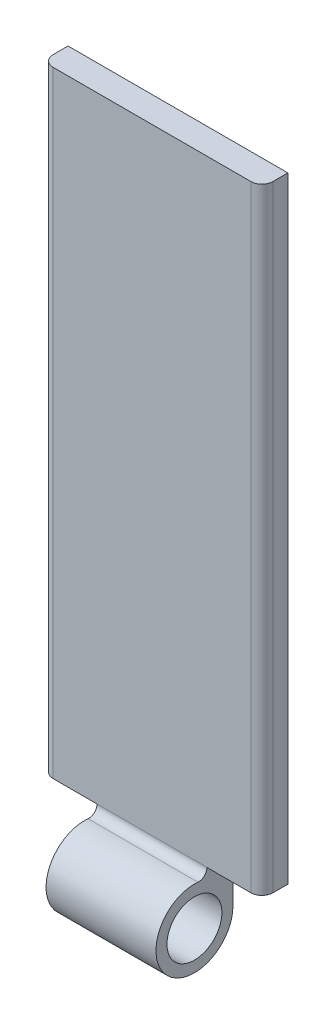
SolidWorks part; units mm, degrees
ref_plane "Front Plane" through (0, 0, 0) normal (0, 0, 1) x (1, 0, 0)
ref_plane "Top Plane" through (0, 0, 0) normal (0, 1, 0) x (1, 0, 0)
ref_plane "Right Plane" through (0, 0, 0) normal (1, 0, 0) x (0, 0, -1)
sketch "Sketch2" plane through (0, 0, 0) normal (1, 0, 0) x (0, 0, -1)
  line L0 (0.7234, 2.6893) -> (0.7234, 38.2813)
  line L1 (2.2225, 0) -> (2.2225, 38.2813)
  line L2 (2.2225, 38.2813) -> (0.7234, 38.2813)
  circle A0 centre (0, 0) radius 1.5875
  arc A1 (0.202, 2.2133) -> (2.2225, 0) centre (0, 0) ccw
  arc A2 (0.7234, 2.6893) -> (0.202, 2.2133) centre (0.2455, 2.6893) cw
  point P9 (0, 0)
  dimension "D2" = 3.175
  dimension "D3" = 2.2225
extrude "Boss-Extrude1" add sketch "Sketch2" along normal blind 12.7
sketch "Sketch4" plane through (0, 0, -0.7234) normal (0, 0, 1) x (1, 0, 0)
  line L0 (0, 0) -> (12.7, 0)
  line L1 (12.7, 2.6893) -> (0, 2.6893) construction
  line L2 (3.175, -2.6893) -> (9.525, -2.6893)
  line L3 (3.175, -2.6893) -> (3.175, 2.6893)
  line L4 (3.175, 2.6893) -> (9.525, 2.6893)
  line L5 (9.525, -2.6893) -> (9.525, 2.6893)
  line L6 (3.175, -2.6893) -> (9.525, 2.6893) construction
  line L7 (3.175, 2.6893) -> (9.525, -2.6893) construction
  line L9 (0, 2.6893) -> (3.175, 2.6893)
  line L10 (0, 2.6893) -> (0, -2.6893)
  line L11 (0, -2.6893) -> (3.175, -2.6893)
  line L12 (3.175, 2.6893) -> (3.175, -2.6893)
  line L13 (9.525, 2.6893) -> (12.9542, 2.6893)
  line L14 (9.525, 2.6893) -> (9.525, -2.6893)
  line L15 (9.525, -2.6893) -> (12.9542, -2.6893)
  line L16 (12.9542, 2.6893) -> (12.9542, -2.6893)
  point P4 (6.35, 0)
  dimension "D1" = 6.35
extrude "Cut-Extrude3" cut sketch "Sketch4" against normal blind 12.7 and the other way blind 12.7 contours L12 L9 L10 L11 | L13 L16 L15 L14
fillet "Fillet4" radius 0.635 2 edges at (0, 20.4853, -0.7234) (12.7, 20.4853, -0.7234)
sketch "Sketch11" plane through (0, 0, -2.2225) normal (0, 0, -1) x (-1, 0, 0)
  line L0 (-12.7, 14.2291) -> (0, 14.2291) construction
  line L1 (-12.7, 2.6893) -> (-12.7, 38.2813) construction
  line L2 (0, 2.6893) -> (0, 38.2813) construction
  line L4 (-7.5919, 8.864) -> (-5.1081, 8.864)
  line L5 (-7.5919, 8.864) -> (-7.5919, 19.5942)
  line L6 (-7.5919, 19.5942) -> (-5.1081, 19.5942)
  line L7 (-5.1081, 8.864) -> (-5.1081, 19.5942)
  line L8 (-7.5919, 8.864) -> (-5.1081, 19.5942) construction
  line L9 (-7.5919, 19.5942) -> (-5.1081, 8.864) construction
  point P6 (-6.35, 14.2291)
scale "Scale1" scale about centroid uniform scaling yes scale factor 3
